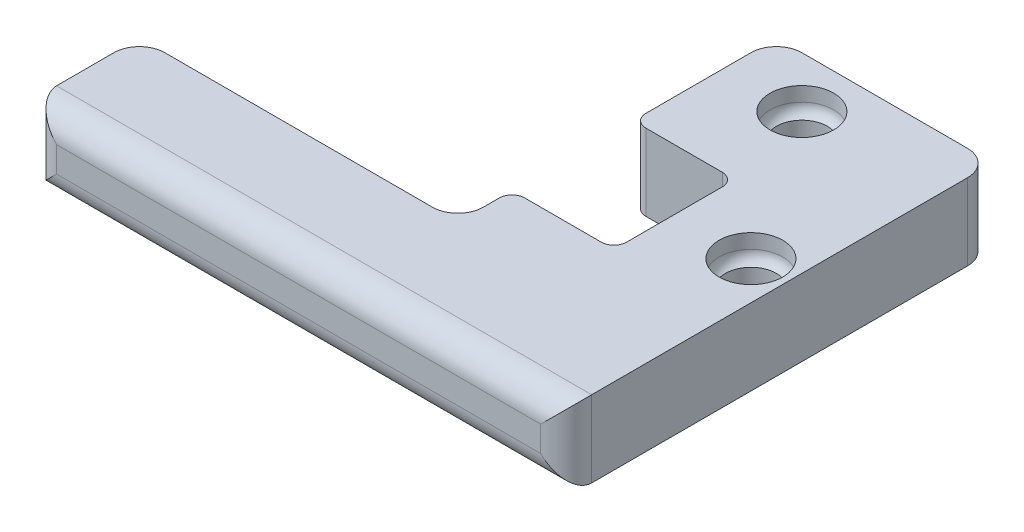
SolidWorks part; units mm, degrees
ref_plane "Front Plane" through (0, 0, 0) normal (0, 0, 1) x (1, 0, 0)
ref_plane "Top Plane" through (0, 0, 0) normal (0, 1, 0) x (1, 0, 0)
ref_plane "Right Plane" through (0, 0, 0) normal (1, 0, 0) x (0, 0, -1)
sketch "Sketch1" plane through (0, 0, 0) normal (0, 1, 0) x (1, 0, 0)
  line L1 (-8.5, 12.5) -> (8.5, 12.5)
  line L2 (-8.5, 12.5) -> (-8.5, -12.5)
  line L3 (-8.5, -12.5) -> (8.5, -12.5)
  line L4 (8.5, 12.5) -> (8.5, -12.5)
  line L5 (-8.5, 12.5) -> (8.5, -12.5) construction
  line L6 (-8.5, -12.5) -> (8.5, 12.5) construction
  line L7 (8.5, -12.5) -> (-33.5, -12.5)
  line L8 (8.5, -12.5) -> (8.5, -21)
  line L9 (8.5, -21) -> (-33.5, -21)
  line L10 (-33.5, -12.5) -> (-33.5, -21)
  point P0 (0, 0)
  dimension "D1" = 25
  dimension "D2" = 17
  dimension "D3" = 8.5
  dimension "D4" = 42
extrude "Boss-Extrude1" add sketch "Sketch1" along normal blind 6 contours L7 L10 L9 L8 L3 | L4 L1 L2 L3 region at (0, 0, 0) region at (-12.5, 0, 16.75)
sketch "Sketch2" plane through (0, 6, 0) normal (0, 1, 0) x (1, 0, 0)
  line L0 (-8.5, -12.5) -> (5.5, -12.5) construction
  line L1 (5.5, -12.5) -> (5.5, 8.5) construction
  line L2 (5.5, 8.5) -> (-2.5, 8.5) construction
  circle A0 centre (-2.5, 8.5) radius 2
  circle A1 centre (5.5, -3.5) radius 2
  dimension "D5" = 4
  dimension "D1" = 14
  dimension "D2" = 21
  dimension "D3" = 8
  dimension "D4" = 9
extrude "Cut-Extrude1" cut sketch "Sketch2" against normal through all
fillet "Fillet2" radius 2 4 edges at (-33.5, 3, 21) (-12.5, 6, 21) (8.5, 3, 21) (-12.5, 0, 21)
fillet "Fillet1" radius 2 4 edges at (-8.5, 3, 12.5) (-8.5, 3, -12.5) (8.5, 3, -12.5) (-33.5, 3, 12.5)
sketch "Sketch3" plane through (0, 0, 0) normal (0, -1, 0) x (1, 0, 0)
  circle A0 centre (5.5, 3.5) radius 2.5
  circle A1 centre (-2.5, -8.5) radius 2.5
  dimension "D1" = 5
extrude "Cut-Extrude2" cut sketch "Sketch3" against normal through all from offset 4 offset against normal yes
fillet "Fillet3" radius 1 2 edges at (-2.5, 4, -11) (5.5, 4, 1)
chamfer "Chamfer1" distance 0.5 angle 45 2 edges at (-2.5, 0, -6.5) (5.5, 0, 5.5)
sketch "Sketch4" plane through (0, 6, 0) normal (0, 1, 0) x (1, 0, 0)
  line L0 (5.5, -3.5) -> (-4.5, -3.5) construction
  line L2 (-8.5, 1.25) -> (-0.5, 1.25)
  line L3 (-8.5, 1.25) -> (-8.5, -8.25)
  line L4 (-8.5, -8.25) -> (-0.5, -8.25)
  line L5 (-0.5, 1.25) -> (-0.5, -8.25)
  line L6 (-8.5, 1.25) -> (-0.5, -8.25) construction
  line L7 (-8.5, -8.25) -> (-0.5, 1.25) construction
  dimension "D1" = 10
  dimension "D2" = 8
  dimension "D3" = 9.5
extrude "Cut-Extrude3" cut sketch "Sketch4" against normal through all
fillet "Fillet4" radius 1 4 edges at (-8.5, 3, -1.25) (-0.5, 3, -1.25) (-0.5, 3, 8.25) (-8.5, 3, 8.25)
